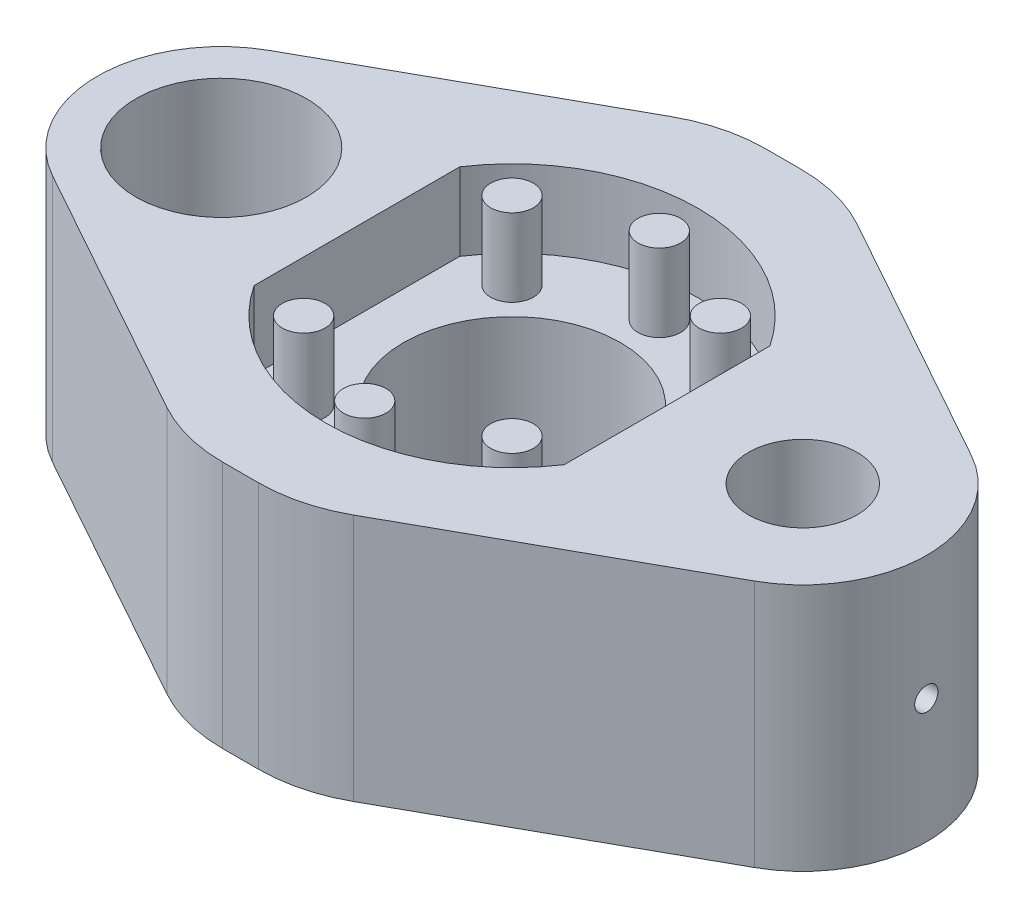
SolidWorks part; units mm, degrees
ref_plane "Front Plane" through (0, 0, 0) normal (0, 0, 1) x (1, 0, 0)
ref_plane "Top Plane" through (0, 0, 0) normal (0, 1, 0) x (1, 0, 0)
ref_plane "Right Plane" through (0, 0, 0) normal (1, 0, 0) x (0, 0, -1)
sketch "Sketch1" plane through (0, 0, 0) normal (0, 1, 0) x (1, 0, 0)
  line L0 (-20, 13.2665) -> (-20, -13.2665)
  line L1 (20, 13.2665) -> (20, -13.2665)
  line L2 (-7.5, -35) -> (7.5, -35)
  line L3 (-7.5, -35) -> (-45.2788, -13.9818)
  line L4 (0, 105.5868) -> (0, -105.5868) construction
  line L5 (7.5, -35) -> (45.2788, -13.9818)
  line L6 (-86.2788, 0) -> (86.2788, 0) construction
  line L7 (-7.5, 35) -> (7.5, 35)
  line L8 (7.5, 35) -> (45.2788, 13.9818)
  line L9 (-7.5, 35) -> (-45.2788, 13.9818)
  circle A0 centre (0, 0) radius 14
  arc A1 (-20, -13.2665) -> (20, -13.2665) centre (0, 0) ccw
  arc A2 (20, 13.2665) -> (-20, 13.2665) centre (0, 0) ccw
  arc A3 (-45.2788, 13.9818) -> (-45.2788, -13.9818) centre (-37.5, 0) ccw
  circle A4 centre (-37.5, 0) radius 11
  circle A5 centre (37.5, 0) radius 7
  arc A6 (45.2788, 13.9818) -> (45.2788, -13.9818) centre (37.5, 0) cw
  point P13 (0, -35)
  point P16 (0, 0)
  point P24 (0, 0)
  dimension "D1" = 28
  dimension "D2" = 48
  dimension "D4" = 22
  dimension "D5" = 32
  dimension "D9" = 14
  dimension "D3" = 40
  dimension "D6" = 37.5
  dimension "D7" = 15
  dimension "D8" = 35
extrude "Extrude2" add sketch "Sketch1" along normal blind 32 contours A6 L8 L7 L9 A3 L3 L2 L5 A2 L1 A1 L0 A4 region at (-25.7677, 0, 23.3736)
extrude "Extrude3" add sketch "Sketch" along normal offset from surface (22 mm away) 10 contours L1 A2 L0 A1 A0 region at (0, 0, -23.3752) up to face at (0, 32, 0)
sketch "Sketch" plane through (0, 0, 0) normal (0, 1, 0) x (1, 0, 0) same geometry as "Sketch1"
fillet "Fillet1" radius 20 4 edges at (-7.5, 16, -35) (7.5, 16, -35) (7.5, 16, 35) (-7.5, 16, 35)
sketch "Sketch5" plane through (0, 22, 0) normal (0, 1, 0) x (1, 0, 0)
  circle A0 centre (13.435, 13.435) radius 2.75
  dimension "D1" = 5.5
extrude "Extrude5" add sketch "Sketch5" along normal up to surface (10 mm away) up to face at (0, 32, 0)
pattern_circular "CirPattern1" count 3 every 45 about axis through (0, 22, 0) along (0, 1, 0) of "Extrude5"
mirror "Mirror1" about plane through (0, 0, 0) normal (0, 0, 1) of "Extrude5", "CirPattern1"
sketch3d "3DSketch3"
  circle A0 centre (37.5, 16, 0) radius 8
  circle A1 centre (37.5, 16, 0) radius 1.5
  circle A2 centre (37.5, 32, 0) radius 7 construction
  point P3 (37.5, 39, 0)
  point P5 (39, 16, 0)
  point P7 (37.5, 24, 0)
  dimension "D1" = 16
  dimension "D2" = 16
  dimension "D3" = 3
extrude "Extrude10" cut sketch "3DSketch3" along direction (0, 1, 0) on the side against the normal mid plane 3 contours A0
extrude "Extrude11" cut sketch "Sketch" along direction (1, 0, 0) on the side of the normal through all contours A1
sketch3d "Sketch" same geometry as "3DSketch3"
